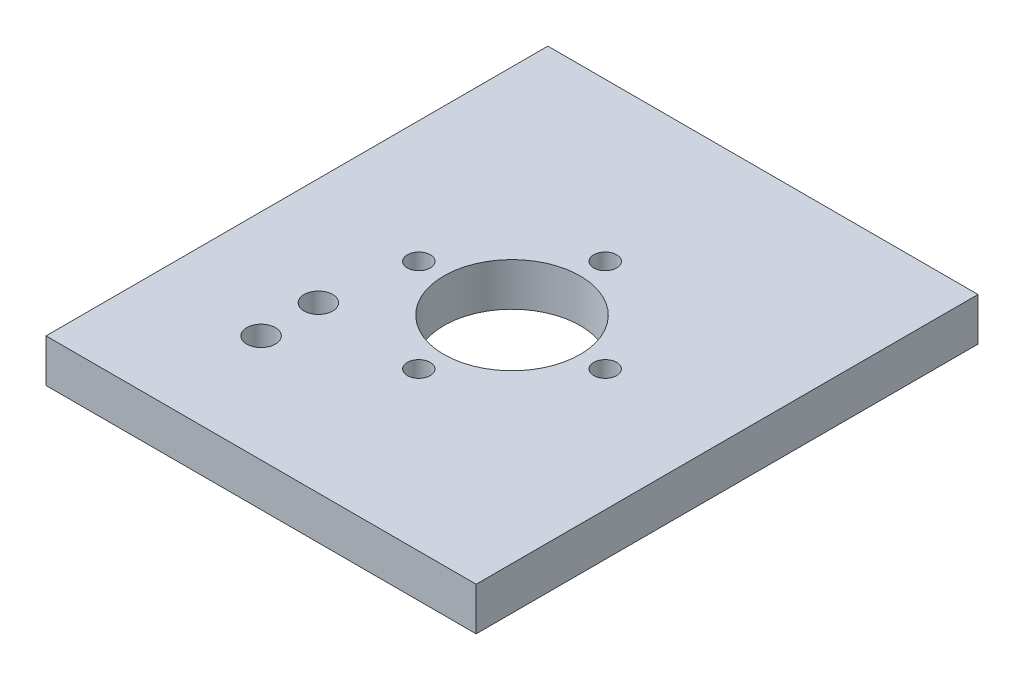
SolidWorks part; units mm, degrees
ref_plane "Front Plane" through (0, 0, 0) normal (0, 0, 1) x (1, 0, 0)
ref_plane "Top Plane" through (0, 0, 0) normal (0, 1, 0) x (1, 0, 0)
ref_plane "Right Plane" through (0, 0, 0) normal (1, 0, 0) x (0, 0, -1)
sketch "Sketch1" plane through (0, 0, 0) normal (0, 1, 0) x (1, 0, 0)
  line L0 (0, -55) -> (0, 55) construction
  line L1 (-30, 35) -> (30, 35)
  line L2 (-30, 35) -> (-30, -35)
  line L3 (-30, -35) -> (30, -35)
  line L4 (30, 35) -> (30, -35)
  line L5 (-30, 35) -> (30, -35) construction
  line L6 (-30, -35) -> (30, 35) construction
  line L7 (-55, 0) -> (55, 0) construction
  line L8 (-15, -20) -> (-15, -12) construction
  circle A0 centre (0, 0) radius 13 construction
  circle A1 centre (0, 13) radius 1.5 construction
  circle A2 centre (13, 0) radius 1.5 construction
  circle A3 centre (0, -13) radius 1.5 construction
  circle A4 centre (-13, 0) radius 1.5 construction
  circle A7 centre (0, 0) radius 9.5
  circle A8 centre (-17.5, 25) radius 2.5 construction
  circle A9 centre (17.5, 25) radius 2.5 construction
  circle A10 centre (17.5, -25) radius 2.5 construction
  circle A11 centre (-17.5, -25) radius 2.5 construction
  circle A12 centre (-50, 25) radius 2.5 construction
  circle A13 centre (-50, -25) radius 2.5 construction
  circle A14 centre (50, -25) radius 2.5 construction
  circle A15 centre (50, 25) radius 2.5 construction
  circle A16 centre (-15, -20) radius 2
  circle A17 centre (-15, -12) radius 2
  point P34 (-15, -12)
  dimension "D1" = 26
  dimension "D2" = 3
  dimension "D4" = 19
  dimension "D7" = 5
  dimension "D10" = 5
  dimension "D13" = 8
  dimension "D15" = 15
  dimension "D16" = 4
  dimension "D5" = 17.5
  dimension "D6" = 60
  dimension "D8" = 70
  dimension "D9" = 25
  dimension "D11" = 50
  dimension "D12" = 25
  dimension "D14" = 15
  dimension "D3" = 4
extrude "Boss-Extrude1" add sketch "Sketch1" along normal blind 6
hole_wizard "CSK for M3 Flat Head Machine Screw1" positions "Sketch7" profile "Sketch8" countersink size "M3" standard "ANSI Metric" end condition through all
sketch "Sketch7" plane through (0, 0, 0) normal (0, -1, 0) x (-1, 0, 0)
  point P0 (-13, 0)
  point P3 (0, -13)
  point P6 (13, 0)
  point P9 (0, 13)
sketch "Sketch8" plane through (13, 0, 0) normal (1, 0, 0) x (0, 0, -1)
  line L0 (0, 0) -> (0, 6)
  line L1 (0, 6) -> (1.6, 6)
  line L2 (1.6, 6) -> (1.6, 1.55)
  line L3 (1.6, 1.55) -> (3.15, 0)
  line L5 (3.15, 0) -> (0, 0)
  line L6 (-1.6, 1.55) -> (-3.15, 0) construction
  line L11 (0, -6.35) -> (0, 107.95) construction
  dimension "Thru Hole Dia." = 3.2
  dimension "Thru Hole Depth" = 6
  dimension "Near C'Sink Dia." = 6.3
  dimension "Near C'Sink Angle" = 90
sketch "Sketch9" plane through (0, 0, 0) normal (0, 1, 0) x (1, 0, 0)
  line L0 (0, -55) -> (0, 55) construction
  line L1 (-55, 0) -> (55, 0) construction
  circle A0 centre (17.5, 25) radius 6
  circle A1 centre (-17.5, 25) radius 6
  circle A2 centre (-17.5, -25) radius 6
  circle A3 centre (17.5, -25) radius 6
  dimension "D1" = 12
equation "\"testbed_height\" = 91.50mm"
equation "\"plate_thickness\" = 6mm"
equation "\"main_body_splay_length\" = 48.5mm"
equation "\"splay_shaft_length_no_wires\" = 10mm"
equation "\"splay_shaft_length_wires\" = 6.5mm"
equation "\"timing_pulley_offset\" = 0mm"
equation "\"effective_motor_length\" = \"timing_pulley_offset\" + \"splay_shaft_length_no_wires\" + \"main_body_splay_length\""
equation "\"80_20_side\" = 25.4mm"
equation "\"80_20_length\" = 152.4mm"
equation "\"80_20_optic_mount_length\" = \"80_20_length\" - 25.4mm"
equation "\"optic_board_hole_size\" = 6.35mm"
equation "\"total_mounting_length\" = \"testbed_height\" - \"effective_motor_length\" - \"80_20_side\""
equation "\"mounting_vertical_portion_height\" = \"total_mounting_length\" - 2 * \"plate_thickness\""
equation "\"face_mount_width\" = 15.25mm"
equation "\"center_dist_to_face_mount_vertical_screws\" = 5mm"
equation "\"D1@Boss-Extrude1\"=\"plate_thickness\""
